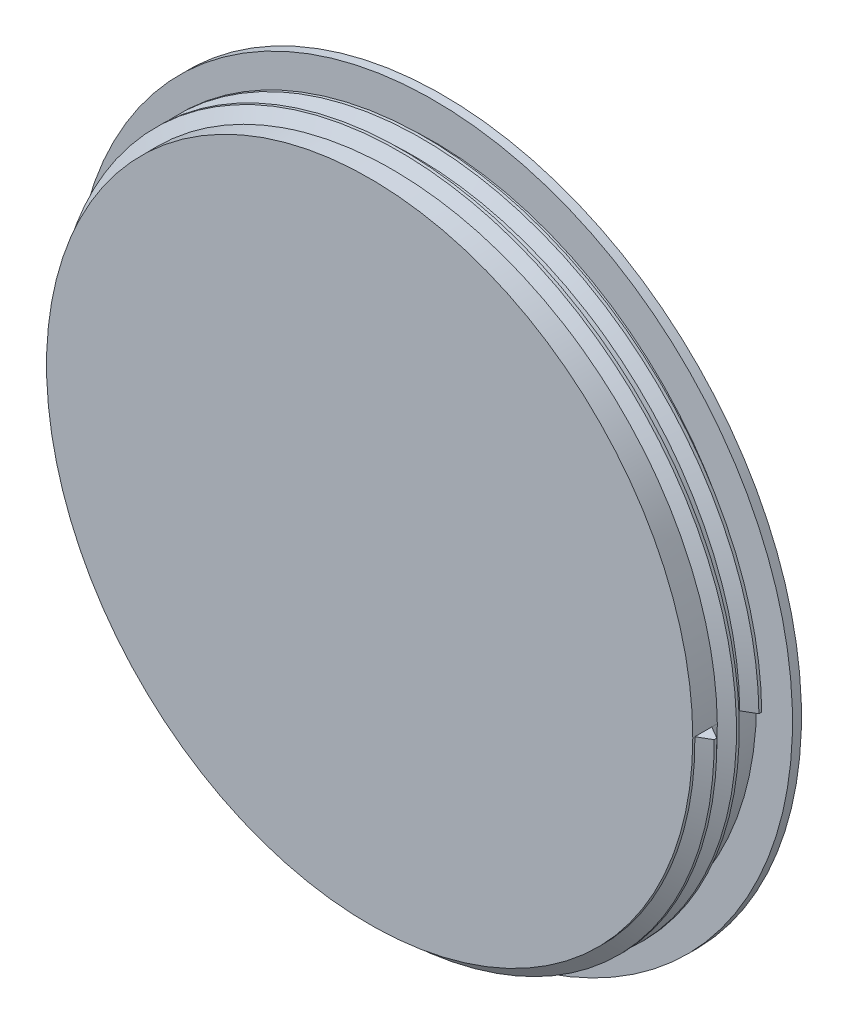
SolidWorks part; units mm, degrees
ref_plane "Plan de face" through (0, 0, 0) normal (0, 0, 1) x (1, 0, 0)
ref_plane "Plan de dessus" through (0, 0, 0) normal (0, 1, 0) x (1, 0, 0)
ref_plane "Plan de droite" through (0, 0, 0) normal (1, 0, 0) x (0, 0, -1)
sketch "Sketch1" plane through (0, 0, 0) normal (0, 0, 1) x (1, 0, 0)
  circle A0 centre (0, 0) radius 36
  dimension "D1" = 72
extrude "Boss-Extrude1" add sketch "Sketch1" along normal blind 7.1095
sketch "Sketch2" plane through (0, 0, 0) normal (0, 0, -1) x (-1, 0, 0)
  circle A0 centre (0, 0) radius 40
  circle A1 centre (0, 0) radius 36 construction
  dimension "D1" = 4
extrude "Boss-Extrude2" add sketch "Sketch2" along normal blind 1
thread "Thread1" pitch 2.5 method extrude profile "Thread Profile1" start angle 0, offset 0, length 5, pitch 2.5, diameter 72
ref_plane "Plane1" through (36, 0, 0) normal (0, -1, 0) x (1, 0, 0)
sketch "Thread Profile1" plane through (36, 0, 0) normal (0, -1, 0) x (1, 0, 0)
  line L0 (0, 0) -> (0, 2.5) construction
  line L1 (0, 0) -> (1.3532, 0.7812)
  line L2 (1.3532, 0.7812) -> (1.3532, 1.0937)
  line L3 (1.3532, 1.0937) -> (0, 1.875)
  line L4 (1.3532, 0.9375) -> (0, 0.9375) construction
  line L11 (0, 0) -> (0, 1.875)
  point P2 (0, 0)
  dimension "Pitch" = 2.5
  dimension "Profile_Angle" = 60
  dimension "Profile_Land" = 0.3125
  dimension "Profile_Height" = 1.3532
sketch "Sketch3" plane through (0, 0, -1) normal (0, 0, -1) x (-1, 0, 0)
  line L0 (0, 40) -> (0, -40) construction
  line L2 (-4, 20) -> (4, 20)
  line L3 (-4, 20) -> (-4, -20)
  line L4 (-4, -20) -> (4, -20)
  line L5 (4, 20) -> (4, -20)
  circle A0 centre (0, 0) radius 40 construction
  point P12 (0, 0)
  dimension "D1" = 4
  dimension "D2" = 4
  dimension "D3" = 20
  dimension "D4" = 20
extrude "Boss-Extrude3" add sketch "Sketch3" along normal blind 7
fillet "Fillet1" radius 2.5 8 edges at (0, -20, -8) (-4, 0, -8) (0, 20, -8) (4, 0, -8) (0, -20, -1) (0, 20, -1) (4, 0, -1) (-4, 0, -1)
